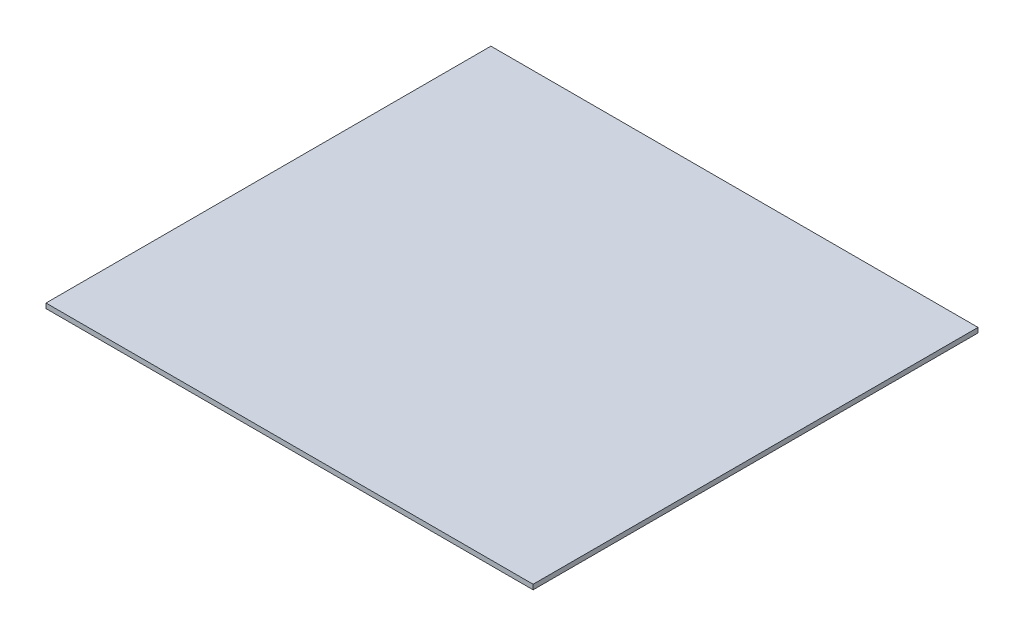
SolidWorks part; units mm, degrees
ref_plane "Front Plane" through (0, 0, 0) normal (0, 0, 1) x (1, 0, 0)
ref_plane "Top Plane" through (0, 0, 0) normal (0, 1, 0) x (1, 0, 0)
ref_plane "Right Plane" through (0, 0, 0) normal (1, 0, 0) x (0, 0, -1)
sketch "Sketch1" plane through (0, 0, 0) normal (0, 1, 0) x (1, 0, 0)
  line L1 (0, 0) -> (300, 0)
  line L2 (0, 0) -> (0, 274)
  line L3 (0, 274) -> (300, 274)
  line L4 (300, 0) -> (300, 274)
  line L21 (0, 0) -> (300, 0)
  dimension "D1" = 300
  dimension "D2" = 274
extrude "Boss-Extrude1" add sketch "Sketch1" along normal blind 3 contours L2 L1 L4 L3 region at (150, 0, -137)
